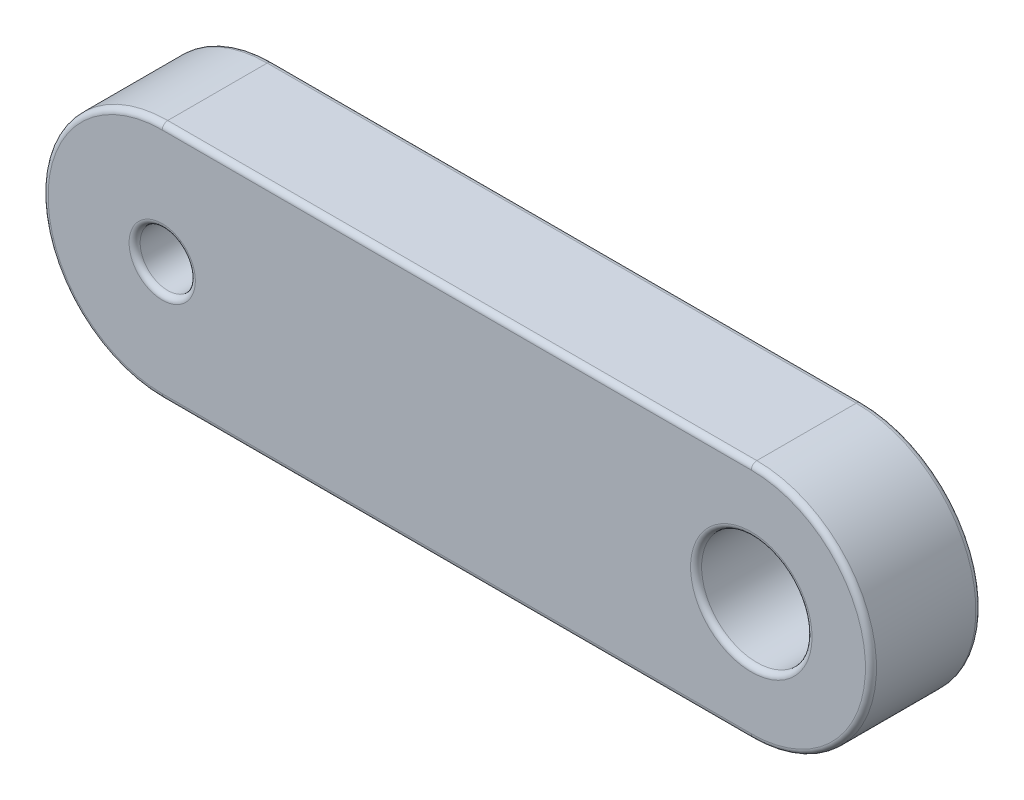
SolidWorks part; units mm, degrees
ref_plane "Płaszczyzna przednia" through (0, 0, 0) normal (0, 0, 1) x (1, 0, 0)
ref_plane "Płaszczyzna górna" through (0, 0, 0) normal (0, 1, 0) x (1, 0, 0)
ref_plane "Płaszczyzna prawa" through (0, 0, 0) normal (1, 0, 0) x (0, 0, -1)
sketch "Szkic1" plane through (0, 0, 0) normal (0, 0, 1) x (1, 0, 0)
  line L0 (-8, 0) -> (8, 0) construction
  line L1 (-8, 3.25) -> (8, 3.25)
  line L2 (-8, -3.25) -> (8, -3.25)
  arc A0 (-8, 3.25) -> (-8, -3.25) centre (-8, 0) ccw
  arc A1 (8, -3.25) -> (8, 3.25) centre (8, 0) ccw
  circle A2 centre (-8, 0) radius 0.75
  circle A3 centre (8, 0) radius 1.5
  point P2 (0, 0)
  dimension "D3" = 3
  dimension "D4" = 1.5
  dimension "D1" = 16
  dimension "D2" = 6.5
extrude "Dodanie-wyciągnięcie1" add sketch "Szkic1" along normal mid plane 3
fillet "Zaokrąglenie1" radius 0.15 12 edges at (9.5, 0, -1.5) (-7.25, 0, -1.5) (0, -3.25, -1.5) (11.25, 0, -1.5) (0, 3.25, -1.5) (-11.25, 0, -1.5) (9.5, 0, 1.5) (0, 3.25, 1.5) (11.25, 0, 1.5) (0, -3.25, 1.5) (-11.25, 0, 1.5) (-7.25, 0, 1.5)
